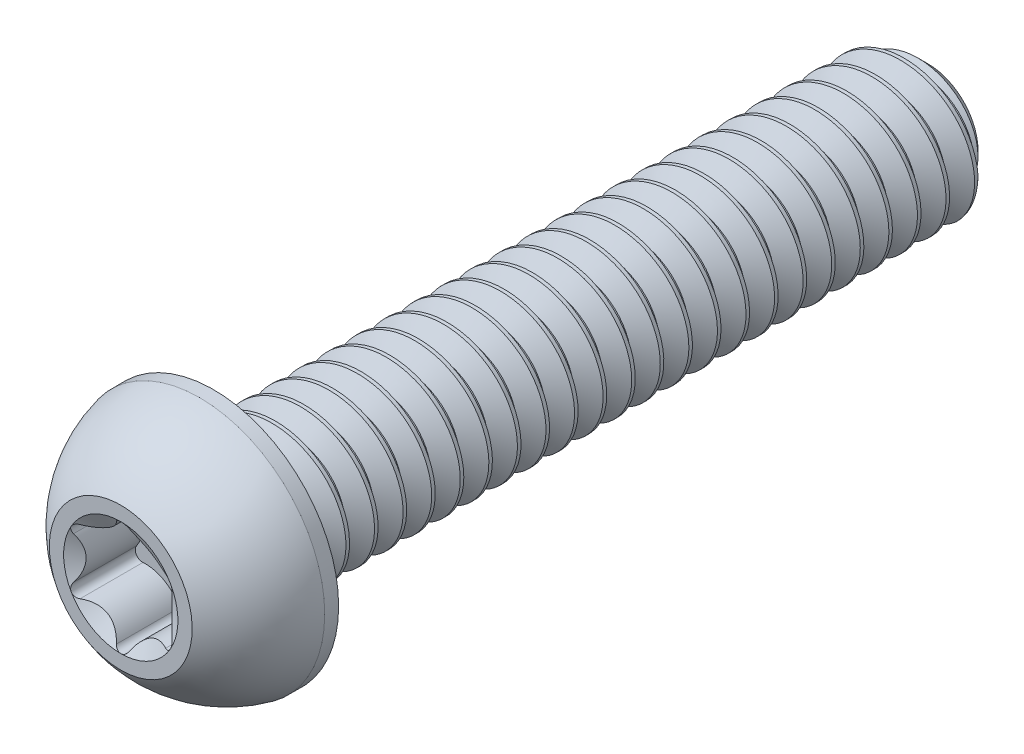
SolidWorks part; units mm, degrees
ref_plane "Front" through (0, 0, 0) normal (0, 0, 1) x (1, 0, 0)
ref_plane "Top" through (0, 0, 0) normal (0, 1, 0) x (1, 0, 0)
ref_plane "Right" through (0, 0, 0) normal (1, 0, 0) x (0, 0, -1)
sketch "Sketch1" plane through (0, 0, 0) normal (1, 0, 0) x (0, 0, -1)
  line L2 (1.3, 1) -> (11.3, 1)
  line L3 (11.3, 1) -> (11.3, 0)
  line L4 (11.3, 0) -> (1.3, 0)
  line L6 (1.105, 1.75) -> (1.3, 1.75) construction
  line L7 (11.3, 1) -> (11.3, -1) construction
  line L8 (0, 0) -> (1.3, 0) construction
  line L9 (1.3, 1.75) -> (1.3, -1.75) construction
  line L11 (1.3, 1) -> (1.3, 0)
  line L14 (0, 0) -> (0, 1) construction
  arc A3 (0, 1) -> (1.105, 1.75) centre (1.4858, 0) cw construction
  dimension "D1" = 0.195
revolve "Revolve1" add sketch "Sketch1" angle 360 mid plane about L4
sketch "Sketch3" plane through (0, 0, -11.3) normal (0, 0, -1) x (-1, 0, 0)
  circle A0 centre (0, 0) radius 1
curve "Helix/Spiral1" pitch 0.4 height 10.4 radius 1 centre (0, 0, -11.3) axis (0, 0, 1) start towards (0, 1, 0)
sketch "Sketch2" plane through (0, 0, 0) normal (1, 0, 0) x (0, 0, -1)
  line L0 (11.3, 1) -> (11.65, 1)
  line L1 (11.65, 1) -> (11.5, 0.7402)
  line L2 (11.5, 0.7402) -> (11.45, 0.7402)
  line L3 (11.45, 0.7402) -> (11.3, 1)
  line L4 (11.375, 0.8701) -> (11.575, 0.8701) construction
  dimension "D1" = 60
  dimension "D2" = 0.05
  dimension "D3" = 0.2
chamfer "Chamfer1" distance 0.3 angle 45 1 edges at (0, 1, -11.3)
sweep "Cut-Sweep1" cut profiles "Sketch2" path "Helix/Spiral1" align with end faces yes
sketch "Sketch7" plane through (0, 0, 0) normal (1, 0, 0) x (0, 0, -1)
  line L0 (0, 0) -> (0, 1) construction
  line L6 (1.105, 1.75) -> (1.3, 1.75) construction
  line L8 (0, 0) -> (1.3, 0) construction
  line L11 (1.3, 1.75) -> (1.3, -1.75) construction
  line L12 (1.105, 1.75) -> (1.3, 1.75)
  line L13 (0, 0) -> (1.3, 0)
  line L15 (1.3, 1.75) -> (1.3, 0)
  line L16 (0, 1) -> (0, 0)
  arc A2 (1.105, 1.75) -> (0, 1) centre (1.4858, 0) ccw construction
  arc A3 (1.105, 1.75) -> (0, 1) centre (1.4858, 0) ccw
revolve "Revolve2" add sketch "Sketch7" angle 360 mid plane about L13
sketch "Sketch11" plane through (0, 0, 0) normal (0, 0, 1) x (1, 0, 0)
  line L0 (0, 0) -> (-0.6928, 0.4)
  line L1 (0, 0) -> (-0.6928, -0.4)
  line L2 (0, 0.8) -> (0, 0.7) construction
  line L3 (0, 0.7) -> (0, 0.6) construction
  line L4 (4.18, 0) -> (-4.18, 0) construction
  circle A0 centre (0, 0) radius 0.6 construction
  circle A1 centre (0, 0) radius 0.7 construction
  circle A2 centre (0, 0) radius 0.8 construction
  arc A3 (-0.6894, 0.2944) -> (-0.6894, -0.2944) centre (-1.1298, 0) cw
  arc A4 (-0.6894, 0.2944) -> (-0.6928, 0.4) centre (-0.6062, 0.35) cw
  arc A5 (-0.6894, -0.2944) -> (-0.6928, -0.4) centre (-0.6062, -0.35) ccw
  dimension "D1" = 1.2
  dimension "D2" = 1.6
  dimension "D3" = 30
extrude "Cut-Extrude4" cut sketch "Sketch11" against normal blind 0.91
pattern_circular "CirPattern1" count 6 over 360 of "Cut-Extrude4"
sketch "Sketch6" plane through (0, 0, 0) normal (0, 0, 1) x (1, 0, 0)
  circle A0 centre (0, 0) radius 0.8 construction
  circle A1 centre (0, 0) radius 0.8
extrude "Cut-Extrude3" cut sketch "Sketch6" against normal blind 0.91 draft 60
sketch "Sketch9" [suppressed] plane through (0, 0, -5.5) normal (0, 0, 1) x (1, 0, 0)
  circle A2 centre (0, 0) radius 5
extrude "Boss-Extrude2" [suppressed] add sketch "Sketch9" against normal offset from surface (13 mm away) 32 up to face at (0, 0.7, -11.3)
sketch "Sketch10" plane through (0, 0, 0) normal (1, 0, 0) x (0, 0, -1)
  line L0 (11.3, 1) -> (11.3, -1) construction
  point P0 (10.7, -1)
  dimension "D1" = 0.6
equation "\"D3@Helix/Spiral1\" = \"Lg@Sketch1\" + \"D4@Helix/Spiral1\""
equation "\"D2@Sketch2\" = \"D4@Helix/Spiral1\" * .125"
equation "\"D3@Sketch2\" = \"D4@Helix/Spiral1\" * .5"
equation "\"D1@Chamfer1\" = \"D4@Helix/Spiral1\" * .75"
equation "\"D1@Sketch1\" = \"Head Ht@Sketch1\" * .15"
equation "\"D1@Sketch10\" = \"D4@Helix/Spiral1\" * 1.5"
equation "\"D2@Sketch11\" = \"Dia@Sketch1\" * .8"
equation "\"D1@Sketch11\" = \"D2@Sketch11\" * .75"
equation "\"D1@Cut-Extrude4\" = \"Head Ht@Sketch1\" * .7"
equation "\"D1@Cut-Extrude3\" = \"D1@Cut-Extrude4\""
